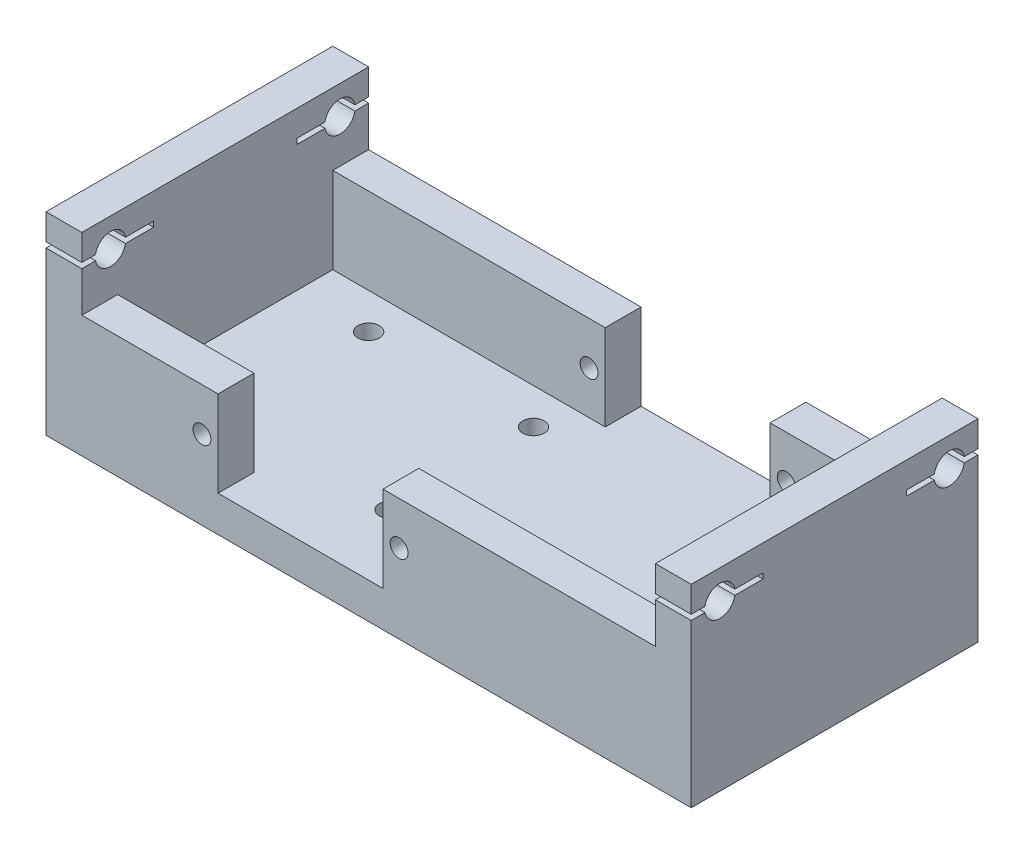
SolidWorks part; units mm, degrees
ref_plane "Front Plane" through (0, 0, 0) normal (0, 0, 1) x (1, 0, 0)
ref_plane "Top Plane" through (0, 0, 0) normal (0, 1, 0) x (1, 0, 0)
ref_plane "Right Plane" through (0, 0, 0) normal (1, 0, 0) x (0, 0, -1)
sketch "Sketch1" plane through (0, 0, 0) normal (0, 1, 0) x (1, 0, 0)
  line L1 (-45, -20) -> (45, -20)
  line L2 (-45, -20) -> (-45, 20)
  line L3 (-45, 20) -> (45, 20)
  line L4 (45, -20) -> (45, 20)
  line L5 (-45, -20) -> (45, 20) construction
  line L6 (-45, 20) -> (45, -20) construction
  point P0 (0, 0)
  dimension "D1" = 90
  dimension "D2" = 40
extrude "Boss-Extrude1" add sketch "Sketch1" along normal blind 5
sketch "Sketch2" plane through (0, 5, 0) normal (0, 1, 0) x (1, 0, 0)
  line L0 (-21, -20) -> (-21, -15)
  line L1 (-45, -20) -> (45, -20) construction
  line L2 (-21, -15) -> (-40, -15)
  line L3 (-45, 20) -> (-45, -20) construction
  line L4 (-40, -15) -> (-40, 15)
  line L6 (-40, 15) -> (-2, 15)
  line L7 (-2, 15) -> (-2, 20)
  line L8 (45, 20) -> (-45, 20) construction
  line L9 (-2, 20) -> (-45, 20)
  line L10 (-45, 20) -> (-45, -20)
  line L11 (-45, -20) -> (-21, -20)
  line L12 (2, -15) -> (40, -15)
  line L13 (45, -20) -> (45, 20) construction
  line L14 (40, -15) -> (40, 15)
  line L15 (40, 15) -> (21, 15)
  line L16 (21, 15) -> (21, 20)
  line L17 (21, 20) -> (45, 20)
  line L18 (45, 20) -> (45, -20)
  line L19 (45, -20) -> (2, -20)
  line L20 (2, -20) -> (2, -15)
  dimension "D1" = 23
  dimension "D2" = 5
  dimension "D3" = 30
  dimension "D4" = 5
  dimension "D5" = 5
  dimension "D6" = 24
  dimension "D9" = 5
extrude "Boss-Extrude2" add sketch "Sketch2" along normal blind 12
sketch "Sketch3" plane through (0, 17, 0) normal (0, 1, 0) x (1, 0, 0)
  line L0 (45, 20) -> (21, 20) construction
  line L1 (45, -20) -> (40, -20)
  line L2 (45, -20) -> (45, 20)
  line L3 (45, 20) -> (40, 20)
  line L4 (40, -20) -> (40, 20)
  line L5 (40, 15) -> (40, -15) construction
  line L6 (-45, -20) -> (-21, -20) construction
  line L7 (-45, 20) -> (-40, 20)
  line L8 (-45, 20) -> (-45, -20)
  line L9 (-45, -20) -> (-40, -20)
  line L10 (-40, 20) -> (-40, -20)
  line L11 (-40, -15) -> (-40, 15) construction
extrude "Boss-Extrude3" add sketch "Sketch3" along normal blind 10
sketch "Sketch5" plane through (-45, 0, 0) normal (-1, 0, 0) x (0, 0, 1)
  line L0 (-20, 27) -> (20, 27) construction
  line L1 (20, 27) -> (20, 0) construction
  line L2 (0, -14.85) -> (0, 14.85) construction
  circle A0 centre (16, 23) radius 2.125
  circle A1 centre (-16, 23) radius 2.125
  dimension "D1" = 4.25
  dimension "D2" = 4
  dimension "D3" = 4
extrude "Cut-Extrude1" cut sketch "Sketch5" against normal through all
sketch "Sketch7" plane through (0, 0, 15) normal (0, 0, -1) x (-1, 0, 0)
  line L0 (-21, 17) -> (-21, 5) construction
  line L1 (2, 17) -> (2, 5) construction
  line L2 (2, 17) -> (40, 17) construction
  line L3 (-40, 17) -> (-21, 17) construction
  circle A0 centre (-23.25, 11) radius 1.25
  circle A1 centre (4.25, 11) radius 1.25
  point P12 (0, 0)
  dimension "D1" = 2.5
  dimension "D2" = 2.25
  dimension "D4" = 6
  dimension "D5" = 2.5
  dimension "D6" = 6
  dimension "D3" = 2.25
extrude "Cut-Extrude3" cut sketch "Sketch7" along normal up to surface (35 mm away) up to face at (3.1667, 15.5, -20)
sketch "Sketch8" plane through (-45, 0, 0) normal (-1, 0, 0) x (0, 0, 1)
  line L0 (20, 27) -> (20, 0) construction
  line L1 (20, 23.375) -> (10, 23.375)
  line L2 (20, 23.375) -> (20, 22.625)
  line L3 (20, 22.625) -> (10, 22.625)
  line L4 (-20, 23.375) -> (-20, 22.625)
  line L5 (-20, 27) -> (-20, 0) construction
  line L6 (10, 23.375) -> (10, 22.625)
  line L7 (-10, 23.375) -> (-10, 22.625)
  line L8 (-10, 23.375) -> (-20, 23.375)
  line L9 (-10, 22.625) -> (-20, 22.625)
  circle A0 centre (16, 23) radius 2.125 construction
  dimension "D1" = 0.75
  dimension "D2" = 0.375
  dimension "D3" = 10
  dimension "D4" = 10
extrude "Cut-Extrude4" cut sketch "Sketch8" against normal through all
sketch "Sketch9" plane through (0, 0, 0) normal (0, -1, 0) x (-1, 0, 0)
  line L0 (45, -20) -> (-45, -20) construction
  line L1 (23.5, -20) -> (19.5, -20)
  line L2 (23.5, -20) -> (23.5, 20)
  line L3 (23.5, 20) -> (19.5, 20)
  line L4 (19.5, -20) -> (19.5, 20)
  line L5 (-45, 20) -> (45, 20) construction
  line L6 (0, -20) -> (0, 19.3326) construction
  line L7 (15, -20) -> (11, -20)
  line L8 (15, -20) -> (15, 20)
  line L9 (15, 20) -> (11, 20)
  line L10 (11, -20) -> (11, 20)
  dimension "D1" = 4
  dimension "D2" = 4
  dimension "D3" = 4.5
  dimension "D4" = 15
extrude "Boss-Extrude4" [suppressed] add sketch "Sketch9" along normal blind 20
sketch "Sketch11" plane through (-1.6583, 0, 0) normal (-1, 0, 0) x (0, 0, 1)
  circle A1 centre (11.5, -14.5) radius 1.25
  circle A2 centre (-16, -14.5) radius 1.25
  circle A3 centre (-16, -7) radius 1.25
  circle A4 centre (11.5, -7) radius 1.25
  dimension "D1" = 2.5
  dimension "D2" = 2.5
  dimension "D3" = 2.5
  dimension "D4" = 7.5
  dimension "D5" = 2.5
  dimension "D6" = 7.5
  dimension "D7" = 27.5
extrude "Cut-Extrude5" [suppressed] cut sketch "Sketch11" against normal through all and the other way through all
sketch "Sketch12" plane through (0, 0, 0) normal (0, -1, 0) x (1, 0, 0)
  line L0 (-45, -20) -> (-45, 20) construction
  line L2 (45, -20) -> (-45, -20) construction
  line L5 (-45, 20) -> (45, 20) construction
  circle A0 centre (-30, 10) radius 1.5
  circle A1 centre (-30, -10) radius 1.5
  circle A2 centre (-7, 10) radius 1.5
  circle A3 centre (-7, -10) radius 1.5
  point P6 (0, 0)
  dimension "D1" = 3
  dimension "D2" = 3
  dimension "D3" = 15
  dimension "D4" = 23
  dimension "D6" = 10
  dimension "D7" = 3
  dimension "D9" = 10
  dimension "D10" = 3
extrude "Cut-Extrude6" cut sketch "Sketch12" against normal through all
sketch "Sketch13" plane through (0, 0, 20) normal (0, 0, 1) x (1, 0, 0)
  line L0 (-21, 17) -> (-21, 5) construction
  circle A1 centre (-23.25, 11) radius 1.25
  circle A2 centre (4.25, 11) radius 1.25
  point P6 (-26.9068, 7.0873)
  point P7 (0, 0)
  point P11 (0, 0)
  dimension "D1" = 2.5
  dimension "D2" = 2.5
  dimension "D3" = 27.5
  dimension "D4" = 2.25
extrude "Cut-Extrude7" cut sketch "Sketch13" against normal up to surface (5 mm away) contours A1 | A2 up to face at (21, 11, 15)
